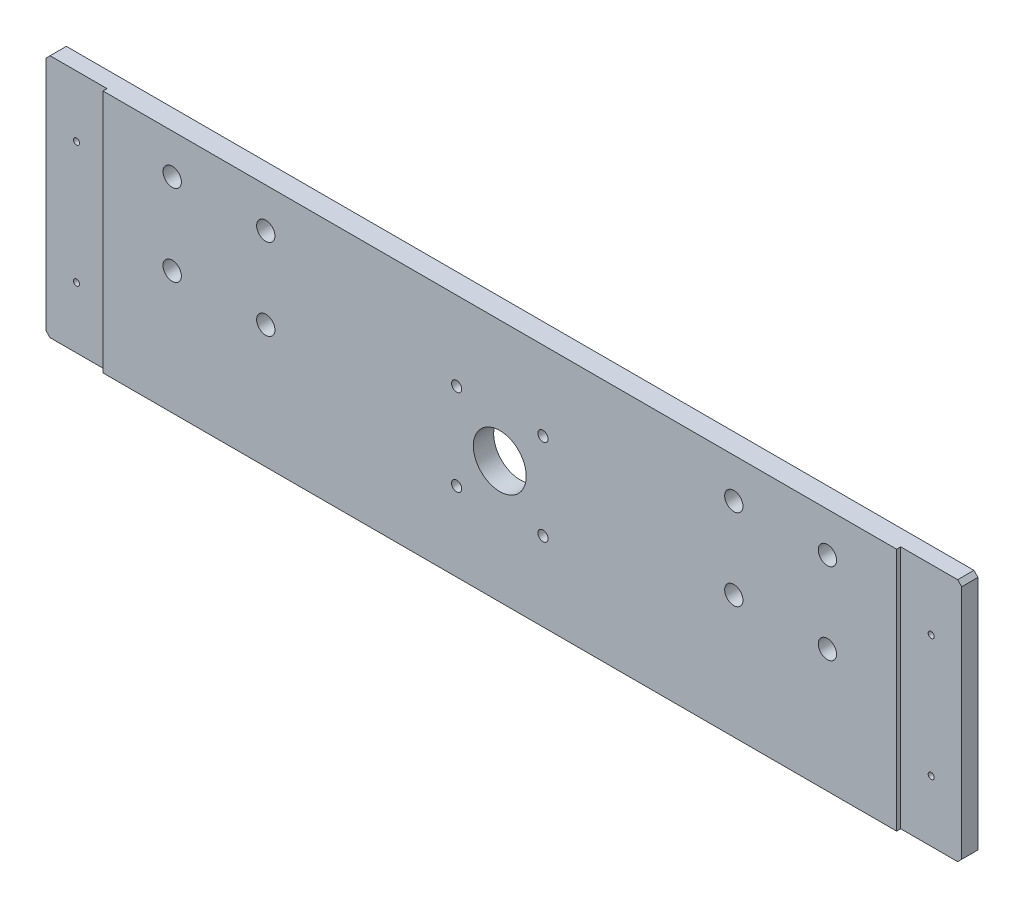
SolidWorks part; units mm, degrees
ref_plane "Piano frontale" through (0, 0, 0) normal (0, 0, 1) x (1, 0, 0)
ref_plane "Piano superiore" through (0, 0, 0) normal (0, 1, 0) x (1, 0, 0)
ref_plane "Piano destro" through (0, 0, 0) normal (1, 0, 0) x (0, 0, -1)
sketch "Schizzo1" plane through (0, 0, 0) normal (0, 0, 1) x (1, 0, 0)
  line L0 (225, 120) -> (225, 0) construction
  line L1 (2, 0) -> (448, 0)
  line L2 (0, 2) -> (0, 118)
  line L3 (2, 120) -> (448, 120)
  line L4 (450, 2) -> (450, 118)
  line L5 (225, 60) -> (199.8765, 85.1235) construction
  line L7 (225, 60) -> (243.5099, 60) construction
  line L21 (0, 118) -> (2, 120)
  line L22 (2, 0) -> (0, 2)
  line L23 (448, 0) -> (450, 2)
  line L24 (448, 120) -> (450, 118)
  line L25 (225, 60) -> (450, 60) construction
  circle A0 centre (225, 60) radius 13
  circle A1 centre (225, 60) radius 30 construction
  circle A2 centre (246.2132, 81.2132) radius 2.5
  circle A3 centre (386, 100.5) radius 4.5
  circle A4 centre (246.2132, 38.7868) radius 2.5
  circle A5 centre (203.7868, 38.7868) radius 2.5
  circle A6 centre (110, 100.5) radius 4.5
  circle A7 centre (110, 60.5) radius 4.5
  circle A8 centre (64, 60.5) radius 4.5
  circle A9 centre (64, 100.5) radius 4.5
  circle A10 centre (386, 60.5) radius 4.5
  circle A11 centre (15, 30) radius 1.5
  circle A12 centre (435, 30) radius 1.5
  circle A13 centre (203.7868, 81.2132) radius 2.5
  circle A14 centre (340, 60.5) radius 4.5
  circle A15 centre (340, 100.5) radius 4.5
  circle A17 centre (435, 90) radius 1.5
  circle A18 centre (15, 90) radius 1.5
  point P0 (0, 0)
  point P1 (450, 120)
  point P2 (0, 120)
  point P3 (450, 0)
  point P13 (203.7868, 81.2132)
  point P14 (246.2132, 81.2132)
  point P15 (203.7868, 38.7868)
  point P17 (246.2132, 38.7868)
  dimension "D4" = 26
  dimension "D15" = 3
  dimension "D17" = 5
  dimension "D8" = 60
  dimension "D1" = 120
  dimension "D2" = 450
  dimension "D3" = 60
  dimension "D5" = 45
  dimension "D14" = 30
  dimension "D16" = 15
extrude "Estrusione-Estrusione1" add sketch "Schizzo1" against normal blind 10
sketch "Schizzo2" plane through (0, 0, 0) normal (0, 0, 1) x (1, 0, 0)
  line L0 (448, 120) -> (2, 120) construction
  line L1 (30, 120) -> (0, 120)
  line L2 (30, 120) -> (30, 0)
  line L3 (30, 0) -> (0, 0)
  line L4 (0, 120) -> (0, 0)
  line L5 (225, 120) -> (225, -23.5993) construction
  line L6 (450, 120) -> (450, 0)
  line L7 (420, 0) -> (450, 0)
  line L8 (420, 120) -> (420, 0)
  line L9 (420, 120) -> (450, 120)
  dimension "D1" = 30
extrude "Taglio-Estrusione1" cut sketch "Schizzo2" against normal blind 2
